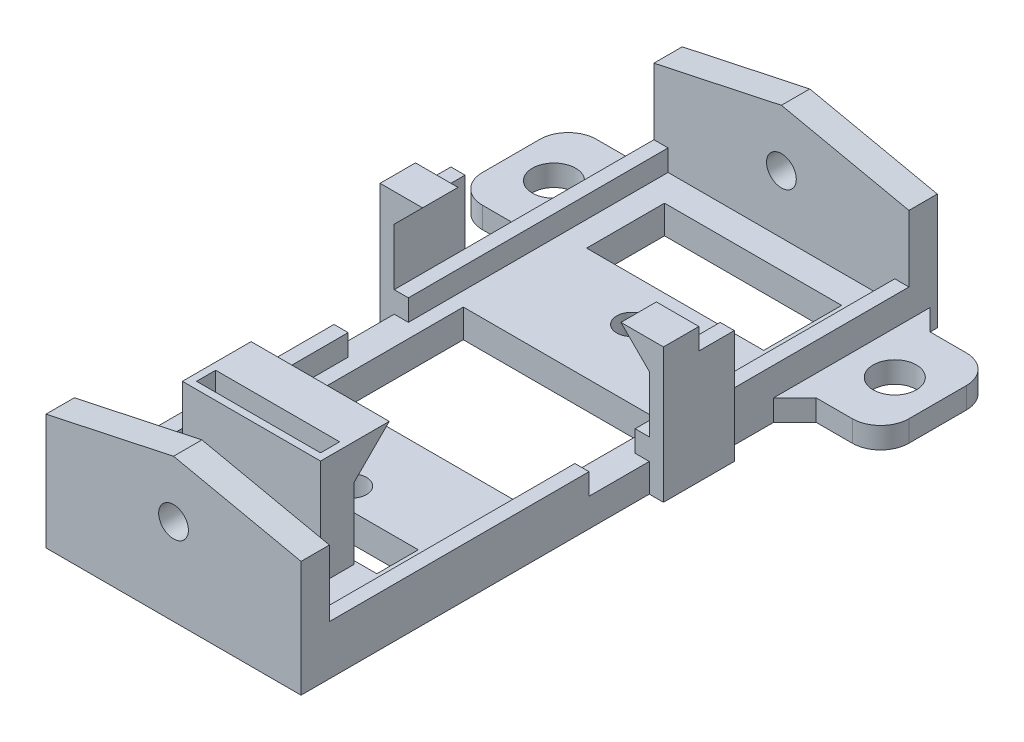
SolidWorks part; units mm, degrees
ref_plane "Front Plane" through (0, 0, 0) normal (0, 0, 1) x (1, 0, 0)
ref_plane "Top Plane" through (0, 0, 0) normal (0, 1, 0) x (1, 0, 0)
ref_plane "Right Plane" through (0, 0, 0) normal (1, 0, 0) x (0, 0, -1)
sketch "Sketch1" plane through (0, 0, 0) normal (0, 0, 1) x (1, 0, 0)
  line L2 (-40.4, 110) -> (0, 118.6383) construction
  line L3 (-18, 114.7896) -> (0, 114.7896)
  line L4 (0, 114.7896) -> (18, 114.7896)
  line L5 (0, 118.6383) -> (40.4, 110) construction
  line L11 (18, 114.7896) -> (18, 121.7896)
  line L12 (18, 121.7896) -> (16, 121.7896)
  line L13 (16, 121.7896) -> (16, 118.7896)
  line L14 (16, 118.7896) -> (-16, 118.7896)
  line L15 (-16, 118.7896) -> (-16, 121.7896)
  line L16 (-16, 121.7896) -> (-18, 121.7896)
  line L17 (-18, 121.7896) -> (-18, 114.7896)
  point P15 (0, 118.7896)
  dimension "D1" = 32
  dimension "D2" = 2
  dimension "D3" = 3
  dimension "D4" = 4
extrude "Boss-Extrude1" add sketch "Sketch1" along normal up to surface (89.8 mm away)
sketch "Sketch2" plane through (0, 114.7896, 0) normal (0, -1, 0) x (1, 0, 0)
  line L0 (18, 89.8) -> (18, 0) construction
  line L5 (-14, 54.9) -> (14, 54.9)
  line L6 (-14, 54.9) -> (-14, 34.9)
  line L7 (-14, 34.9) -> (14, 34.9)
  line L8 (14, 54.9) -> (14, 34.9)
  point P4 (0, 34.9)
  point P8 (18, 44.9)
  point P9 (14, 44.9)
  dimension "D1" = 4
  dimension "D2" = 20
extrude "Cut-Extrude1" cut sketch "Sketch2" against normal up to next
sketch "Sketch3" plane through (-18, 0, 0) normal (-1, 0, 0) x (0, 0, 1)
  line L0 (89.8, 121.7896) -> (0, 121.7896) construction
  line L1 (40.65, 118.7896) -> (49.15, 118.7896)
  line L2 (40.65, 118.7896) -> (40.65, 121.7896)
  line L3 (40.65, 121.7896) -> (49.15, 121.7896)
  line L4 (49.15, 118.7896) -> (49.15, 121.7896)
  line L5 (89.8, 118.7896) -> (0, 118.7896) construction
  point P9 (44.9, 121.7896)
  point P10 (44.9, 121.7896)
  dimension "D1" = 8.5
extrude "Cut-Extrude2" cut sketch "Sketch3" against normal through all
sketch "Sketch4" plane through (0, 118.7896, 0) normal (0, 1, 0) x (1, 0, 0)
  circle A0 centre (0, -25.15) radius 2.1 construction
  circle A1 centre (0, -64.65) radius 2.1 construction
  circle A2 centre (0, -25.15) radius 2.1
  circle A3 centre (0, -64.65) radius 2.1
extrude "Cut-Extrude3" cut sketch "Sketch4" against normal through all
ref_plane "Plane2" through (0, 0, 44.9) normal (0, 0, -1) x (-1, 0, 0)
sketch "Sketch5" plane through (0, 0, 0) normal (0, 0, 1) x (1, 0, 0)
  line L0 (-18, 114.7896) -> (-18, 131.1512)
  line L1 (-56.4, 122.9405) -> (0, 135) construction
  line L2 (-18, 131.1512) -> (0, 135)
  line L3 (0, 135) -> (18, 131.1512)
  line L4 (0, 135) -> (56.4, 122.9405) construction
  line L5 (18, 131.1512) -> (18, 114.7896)
  line L6 (18, 114.7896) -> (-18, 114.7896)
  line L7 (0.6273, 134.8659) -> (54.0273, 123.4479) construction
  line L8 (-54.0273, 123.4479) -> (-0.6273, 134.8659) construction
  circle A0 centre (0, 127) radius 2.1
  dimension "D1" = 4.2
  dimension "D2" = 8
extrude "Boss-Extrude2" add sketch "Sketch5" along normal blind 4
mirror "Mirror1" about plane through (0, 0, 44.9) normal (0, 0, -1) of "Boss-Extrude2"
sketch "Sketch6" plane through (0, 118.7896, 0) normal (0, 1, 0) x (1, 0, 0)
  line L1 (12.5, -19) -> (-12.5, -19)
  line L2 (12.5, -19) -> (12.5, -8)
  line L3 (12.5, -8) -> (-12.5, -8)
  line L4 (-12.5, -19) -> (-12.5, -8)
  point P4 (0, -8)
  dimension "D1" = 11
  dimension "D2" = 25
  dimension "D3" = 8
extrude "Cut-Extrude4" cut sketch "Sketch6" against normal through all
sketch "Sketch8" plane through (0, 118.7896, 0) normal (0, 1, 0) x (1, 0, 0)
  line L0 (16, -85.8) -> (-16, -85.8) construction
  line L1 (8.75, -77.8) -> (-8.75, -77.8)
  line L2 (8.75, -77.8) -> (8.75, -75.1)
  line L3 (8.75, -75.1) -> (-8.75, -75.1)
  line L4 (-8.75, -77.8) -> (-8.75, -75.1)
  line L6 (9.75, -74.1) -> (-9.75, -74.1)
  line L7 (-9.75, -78.8) -> (-9.75, -74.1)
  line L8 (9.75, -78.8) -> (-9.75, -78.8)
  line L9 (9.75, -78.8) -> (9.75, -74.1)
  point P6 (0, -85.8)
  point P7 (0, -77.8)
  dimension "D1" = 8
  dimension "D2" = 2.7
  dimension "D3" = 17.5
  dimension "D4" = 1
extrude "Boss-Extrude3" add sketch "Sketch8" along normal blind 15
sketch "Sketch9" plane through (-9.75, 0, 0) normal (-1, 0, 0) x (0, 0, 1)
  line L0 (74.1, 128.7896) -> (69.1, 133.7896)
  line L1 (74.1, 133.7896) -> (74.1, 118.7896) construction
  line L2 (69.1, 133.7896) -> (74.1, 133.7896)
  line L3 (74.1, 133.7896) -> (74.1, 128.7896)
  dimension "D1" = 5
  dimension "D2" = 45
extrude "Boss-Extrude4" add sketch "Sketch9" against normal up to surface (19.5 mm away) up to face at (9.75, 126.2896, 76.45)
sketch "Sketch13" plane through (0, 118.7896, 0) normal (0, 1, 0) x (1, 0, 0)
  line L4 (-8.75, -77.8) -> (8.75, -77.8)
  line L5 (8.75, -77.8) -> (8.75, -75.1)
  line L6 (8.75, -75.1) -> (-8.75, -75.1)
  line L7 (-8.75, -75.1) -> (-8.75, -77.8)
  line L8 (-8.75, -77.8) -> (8.75, -77.8)
  line L9 (8.75, -77.8) -> (8.75, -75.1)
  line L10 (8.75, -75.1) -> (-8.75, -75.1)
  line L11 (-8.75, -75.1) -> (-8.75, -77.8)
  dimension "D1" = 0
extrude "Cut-Extrude5" cut sketch "Sketch13" against normal through all
sketch "Sketch10" plane through (0, 114.7896, 0) normal (0, 1, 0) x (1, 0, 0)
  line L0 (18, -40.65) -> (18, -4) construction
  line L1 (18, -40.65) -> (20, -40.65)
  line L2 (18, -40.65) -> (18, -30.65)
  line L3 (18, -30.65) -> (20, -30.65)
  line L4 (20, -40.65) -> (20, -30.65)
  line L5 (0, -1000) -> (0, 49000) construction
  line L6 (-18, -30.65) -> (-20, -30.65)
  line L7 (-18, -40.65) -> (-18, -30.65)
  line L8 (-18, -40.65) -> (-20, -40.65)
  line L9 (-20, -40.65) -> (-20, -30.65)
  dimension "D1" = 10
  dimension "D2" = 2
extrude "Boss-Extrude5" add sketch "Sketch10" along normal offset from surface (16 mm away) 3
sketch "Sketch12" plane through (0, 0, 40.65) normal (0, 0, 1) x (1, 0, 0)
  line L0 (20, 129.7896) -> (20, 133.7896)
  line L1 (20, 133.7896) -> (14, 133.7896)
  line L2 (14, 133.7896) -> (18, 129.7896)
  line L3 (18, 129.7896) -> (20, 129.7896)
  line L4 (-18, 133.7896) -> (18, 133.7896) construction
  line L5 (18, 114.7896) -> (18, 131.1512) construction
  line L6 (20, 130.7896) -> (20, 114.7896) construction
  line L7 (18, 130.7896) -> (18, 121.7896) construction
  line L8 (0, -868.0678) -> (0, 49131.9322) construction
  line L9 (-18, 129.7896) -> (-20, 129.7896)
  line L10 (-14, 133.7896) -> (-18, 129.7896)
  line L11 (-20, 133.7896) -> (-14, 133.7896)
  line L12 (-20, 129.7896) -> (-20, 133.7896)
  dimension "D1" = 45
  dimension "D2" = 6
extrude "Boss-Extrude6" add sketch "Sketch12" against normal blind 5
sketch "Sketch14" plane through (0, 114.7896, 0) normal (0, 1, 0) x (1, 0, 0)
  line L0 (-18, -30.65) -> (-18, -4) construction
  line L1 (-18, -4) -> (-30.1, -4)
  line L2 (-18, -4) -> (-18, -20.1)
  line L3 (-18, -20.1) -> (-30.1, -20.1)
  line L4 (-30.1, -4) -> (-30.1, -20.1)
  circle A0 centre (-24.05, -12.05) radius 3.05
  point P9 (-30.1, -12.05)
  point P10 (-24.05, -20.1)
  dimension "D1" = 6.1
  dimension "D2" = 3
  dimension "D3" = 5
extrude "Boss-Extrude7" add sketch "Sketch14" along normal blind 3
mirror "Mirror2" about plane through (0, 0, 0) normal (1, 0, 0) of "Boss-Extrude7"
fillet "Fillet1" radius 4 4 edges at (-30.1, 116.2896, 4) (-30.1, 116.2896, 20.1) (30.1, 116.2896, 4) (30.1, 116.2896, 20.1)
chamfer "Chamfer1" distance 3 angle 45 4 edges at (-18, 116.2896, 20.1) (-18, 116.2896, 4) (18, 116.2896, 4) (18, 116.2896, 20.1)
sketch "Sketch16" plane through (0, 118.7896, 0) normal (0, 1, 0) x (1, 0, 0)
  line L0 (9.75, -74.1) -> (-9.75, -74.1) construction
  line L1 (-12.5, -67.75) -> (12.5, -67.75)
  line L2 (-12.5, -67.75) -> (-12.5, -73.6)
  line L3 (-12.5, -73.6) -> (12.5, -73.6)
  line L4 (12.5, -67.75) -> (12.5, -73.6)
  circle A1 centre (0, -64.65) radius 2.1 construction
  point P4 (0, 0)
  point P9 (0, 0)
  dimension "D1" = 0.5
  dimension "D2" = 1
extrude "Cut-Extrude6" cut sketch "Sketch16" against normal through all
equation "\"width\"= 24"
equation "\"thk\"= 3"
equation "\"holesize\"= 4.2"
equation "\"holedistance\"= ( 20 + 12 ) / 2"
equation "\"threaded_hole\"= 3.9"
equation "\"fillet_radius\"= 2"
equation "\"ground_clearance\"= 25"
equation "\"tire_thk\"= 3"
equation "\"innerwheel_diam\" = \"wheel_diam\"-2*\"tire_thk\""
equation "\"innerwheel_thk\"= 8"
equation "\"wheel_diam\"= 2*(\"width\"/2+\"ground_clearance\")"
equation "\"coloursensor_holesize\"= 2.65"
equation "\"hole_to_edge\" = 4"
equation "\"D1@Sketch5\"=\"holesize\""
